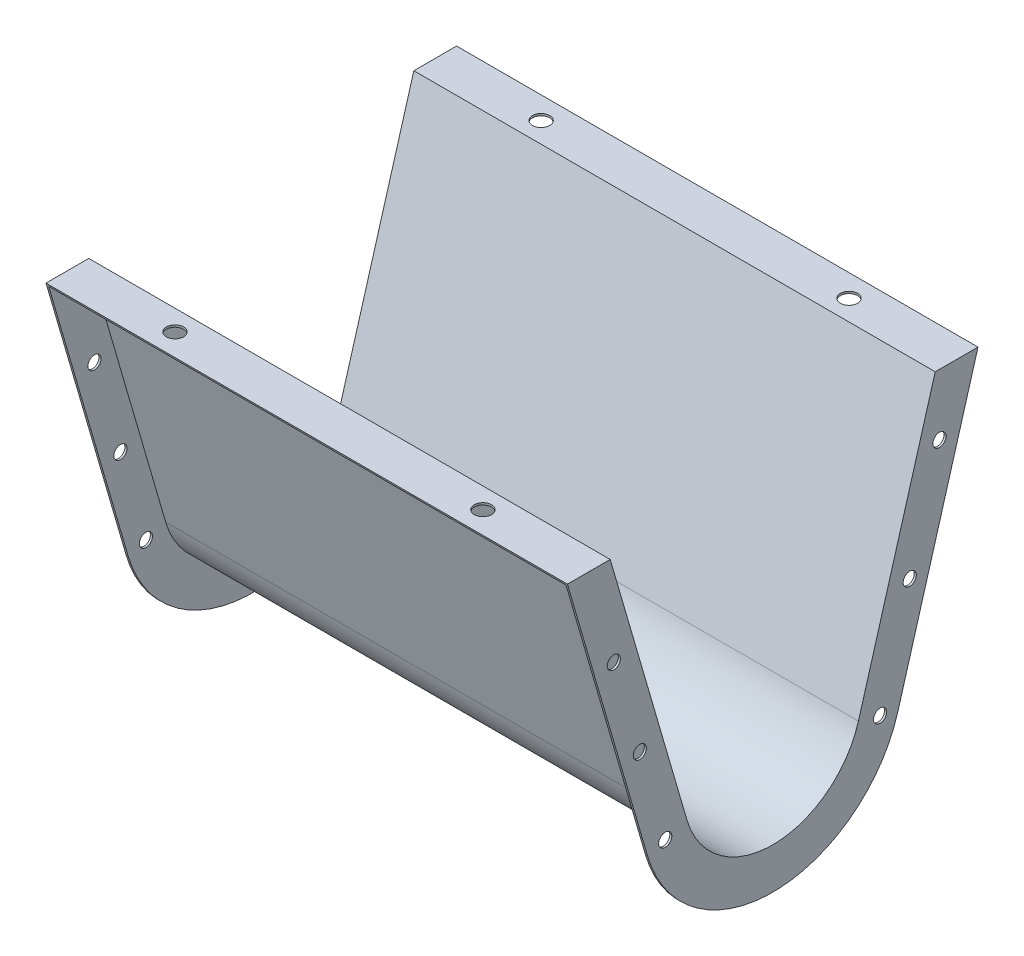
SolidWorks part; units mm, degrees
ref_plane "Front" through (0, 0, 0) normal (0, 0, 1) x (1, 0, 0)
ref_plane "Top" through (0, 0, 0) normal (0, 1, 0) x (1, 0, 0)
ref_plane "Right" through (0, 0, 0) normal (1, 0, 0) x (0, 0, -1)
sketch "Croquis1" plane through (0, 0, 0) normal (1, 0, 0) x (0, 0, -1)
  line L0 (79.1719, 0) -> (100, 0)
  line L1 (100, 0) -> (60.9752, -134.2277)
  line L2 (33.9999, -180) -> (0, -180) construction
  line L3 (0, 0) -> (0, -180) construction
  line L8 (-33.9999, -180) -> (0, -180) construction
  line L9 (-100, 0) -> (-60.9752, -134.2277)
  line L10 (-79.1719, 0) -> (-100, 0)
  line L12 (-79.1719, 0) -> (-41.7704, -128.6442)
  line L13 (79.1719, 0) -> (41.7704, -128.6442)
  line L15 (-73.3572, -20) -> (-41.7704, -128.6442) construction
  line L16 (73.3572, -20) -> (41.7704, -128.6442) construction
  line L17 (0, 0) -> (-100, 0) construction
  line L18 (0, -20) -> (-73.3572, -20) construction
  line L19 (0, 0) -> (100, 0) construction
  line L20 (0, -20) -> (73.3572, -20) construction
  arc A0 (0, -180) -> (60.9752, -134.2277) centre (0, -116.5) ccw
  arc A1 (0, -180) -> (-60.9752, -134.2277) centre (0, -116.5) cw
  arc A2 (0, -160) -> (-41.7704, -128.6442) centre (0, -116.5) cw
  arc A3 (0, -160) -> (41.7704, -128.6442) centre (0, -116.5) ccw
  dimension "D3" = 127
  dimension "D4" = 20
  dimension "D1" = 100
  dimension "D2" = 180
extrude "Saliente-Extruir1" add sketch "Croquis1" along normal blind 254
shell "Vaciado1" thickness 1 removed face at (127, -67.1138, -80.4876) removed face at (127, -157.1138, 0) removed face at (127, -67.1138, 80.4876)
hole_wizard "Taladro de margen para M61" positions "Croquis3D1" profile "Croquis4" hole size "M6" standard "Ansi Metric" end condition through all
sketch3d "Croquis3D1"
  line L0 (253, -1, 79.9225) -> (253, -1, 99.7093) construction
  line L2 (253, -1, 89.8159) -> (253, -131.6798, 52.3433) construction
  line L3 (253, -131.6798, 52.3433) -> (253, -128.9233, 42.7307) construction
  line L4 (0, 0, -89.5859) -> (-0.1028, -131.6317, -52.2935) construction
  line L5 (0, 0, -100) -> (0, 0, -79.1719) construction
  line L6 (-0.1028, -131.6317, -52.2935) -> (1, -128.9233, -42.7307) construction
  point P0 (253, -44.2567, 77.412)
  point P2 (253, -88.4231, 64.7472)
  point P4 (253, -131.6798, 52.3433)
  point P6 (253, -29.75, -81.2229)
  point P8 (253, -81.1189, -66.7461)
  point P10 (253, -131.6317, -52.2935)
  point P12 (1, -29.75, -81.2229)
  point P14 (1, -81.1189, -66.7461)
  point P16 (1, -131.6317, -52.2935)
  point P18 (1, -131.6798, 52.3433)
  point P20 (1, -88.4231, 64.7472)
  point P22 (1, -44.2567, 77.412)
  point P51 (0, 0, 0)
  point P52 (0, 0, 0)
  point P53 (0, 0, 0)
  point P54 (0, 0, 0)
  point P55 (0, 0, 0)
  point P56 (153, -81.1189, -66.7461)
  point P57 (0, 0, 0)
  point P58 (153, -29.75, -81.2229)
  dimension "D1" = 45
  dimension "D2" = 45
  dimension "D3" = 10
  dimension "D4" = 10
sketch "Croquis4" plane through (253, -44.2567, 77.412) normal (0, 1, 0) x (0, 0, 1)
  line L0 (0, 0) -> (0, 1)
  line L1 (0, 1) -> (3.2, 1)
  line L2 (3.2, 1) -> (3.2, 0)
  line L5 (3.2, 0) -> (0, 0)
  line L11 (0, -6.35) -> (0, 107.95) construction
  dimension "Diámetro de taladro hasta el siguiente" = 6.4
  dimension "Profundidad de taladro hasta el siguiente" = 1
hole_wizard "Taladro de margen para M82" positions "Croquis3D2" profile "Croquis6" hole size "M8" standard "Ansi Metric" end condition through all
sketch3d "Croquis3D2"
  line L8 (254, 0, -79.1719) -> (0, 0, -79.1719) construction
  line L9 (51.9992, 0, -89.1719) -> (0, 0, -89.5859) construction
  line L10 (0, 0, -100) -> (0, 0, -79.1719) construction
  line L15 (201.9992, 0, -89.1719) -> (254, 0, -89.1719) construction
  line L16 (254, 0, -100) -> (254, 0, -79.1719) construction
  line L18 (0, 0, 0) -> (154.0584, 0, 0) construction
  line L20 (254, 0, 79.1719) -> (0, 0, 79.1719) construction
  line L21 (0, 0, 79.1719) -> (0, 0, 100) construction
  line L22 (0, 0, 89.5859) -> (52, 0, 89.1719) construction
  line L24 (202, 0, 89.1719) -> (254, 0, 89.5859) construction
  line L25 (254, 0, 79.1719) -> (254, 0, 100) construction
  point P0 (201.9992, 0, -89.1719)
  point P2 (51.9992, 0, -89.1719)
  point P4 (52, 0, 89.1719)
  point P6 (202, 0, 89.1719)
  dimension "D1" = 10
  dimension "D2" = 150
  dimension "D3" = 10
  dimension "D4" = 150
sketch "Croquis6" plane through (201.9992, 0, -89.1719) normal (1, 0, 0) x (0, 0, 1)
  line L0 (0, 0) -> (0, 180)
  line L1 (0, 180) -> (4.2, 180)
  line L2 (4.2, 180) -> (4.2, 0)
  line L5 (4.2, 0) -> (0, 0)
  line L11 (0, -6.35) -> (0, 107.95) construction
  dimension "Diámetro de taladro hasta el siguiente" = 8.4
  dimension "Profundidad de taladro hasta el siguiente" = 180
